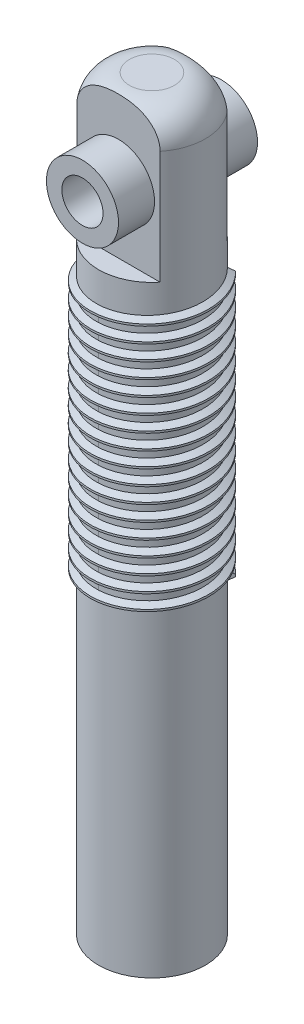
SolidWorks part; units mm, degrees
ref_plane "Piano frontale" through (0, 0, 0) normal (0, 0, 1) x (1, 0, 0)
ref_plane "Piano superiore" through (0, 0, 0) normal (0, 1, 0) x (1, 0, 0)
ref_plane "Piano destro" through (0, 0, 0) normal (1, 0, 0) x (0, 0, -1)
sketch "Schizzo1" plane through (0, 0, 0) normal (0, 0, 1) x (1, 0, 0)
  line L0 (5, -102.5) -> (5, -42.5)
  line L1 (0, 42.5) -> (4.37, 42.5)
  line L2 (0, 42.5) -> (0, -42.5)
  line L3 (5, -102.5) -> (10.37, -102.5)
  line L4 (10.37, 36.5) -> (10.37, -102.5)
  line L5 (5, -42.5) -> (0, -42.5)
  arc A0 (4.37, 42.5) -> (10.37, 36.5) centre (4.37, 36.5) cw
  point P7 (10.37, 42.5)
  dimension "D3" = 6
  dimension "D1" = 10.37
  dimension "D2" = 145
  dimension "D4" = 60
  dimension "D5" = 5
revolve "Rivoluzione1" add sketch "Schizzo1" angle 360 about L2
sketch "Schizzo4" plane through (0, 0, 0) normal (1, 0, 0) x (0, 0, -1)
  line L0 (-10.37, 36.5) -> (-10.37, -102.5) construction
  line L1 (-10.37, 14.5) -> (-6.5, 14.5)
  line L2 (-10.37, 14.5) -> (-10.37, 42.5)
  line L3 (-10.37, 42.5) -> (-6.5, 42.5)
  line L4 (-6.5, 14.5) -> (-6.5, 42.5)
  line L5 (10.37, -102.5) -> (10.37, 36.5) construction
  line L6 (10.37, 14.5) -> (6.5, 14.5)
  line L7 (10.37, 14.5) -> (10.37, 42.5)
  line L8 (10.37, 42.5) -> (6.5, 42.5)
  line L9 (6.5, 14.5) -> (6.5, 42.5)
  line L10 (4.37, 42.5) -> (-4.37, 42.5) construction
  line L11 (0, 0) -> (0, 42.5) construction
  dimension "D1" = 13
  dimension "D2" = 28
extrude "Taglio-Estrusione1" cut sketch "Schizzo4" against normal through all both and the other way through all
sketch "Schizzo6" plane through (0, 0, 6.5) normal (0, 0, 1) x (1, 0, 0)
  line L0 (4.37, 42.5) -> (-4.37, 42.5) construction
  circle A0 centre (0, 27.5) radius 4
  dimension "D1" = 8
  dimension "D2" = 15
extrude "Taglio-Estrusione2" cut sketch "Schizzo6" against normal through all both and the other way through all
ref_plane "Piano1" through (0, 27.5, 0) normal (0, 1, 0) x (1, 0, 0)
ref_plane "Piano2" through (0, 8.5, 0) normal (0, 1, 0) x (1, 0, 0)
sketch "Schizzo22" plane through (0, 8.5, 0) normal (0, 1, 0) x (1, 0, 0)
  circle A0 centre (0, 0) radius 10.37
  dimension "D1" = 20.74
curve "Elica/Spirale1" pitch 3 height 51 radius 10.37 centre (0, 8.5, 0) axis (0, -1, 0) start towards (0.7071, 0, -0.7071)
sketch "Schizzo25" plane through (0, 0, 0) normal (0, 0, 1) x (1, 0, 0)
  line L0 (9.37, 9.9198) -> (9.37, 7.0802)
  line L4 (10.37, -102.5) -> (10.37, 36.5) construction
  line L5 (0, 8.5) -> (17.0247, 8.5) construction
  line L6 (0, 8.5) -> (0, 0) construction
  line L7 (9.37, 7.0802) -> (11.5, 8.31)
  line L8 (11.5, 8.31) -> (11.5, 8.69)
  line L9 (11.5, 8.69) -> (9.37, 9.9198)
  point P3 (9.37, 8.5)
  point P5 (0, 0)
  point P6 (0, 0)
  point P9 (0, 0)
  dimension "D1" = 19
  dimension "D2" = 0.38
  dimension "D3" = 60
  dimension "D4" = 9.37
  dimension "D5" = 11.5
sweep "Sweep1" add profiles "Schizzo25" path "Elica/Spirale1"
sketch "Schizzo26" plane through (0, 0, 6.5) normal (0, 0, 1) x (1, 0, 0)
  circle A0 centre (0, 27.5) radius 7
  circle A1 centre (0, 27.5) radius 4 construction
  circle A2 centre (0, 27.5) radius 4
  dimension "D1" = 14
extrude "Estrusione-Estrusione1" add sketch "Schizzo26" along normal blind 7 and the other way blind 20
